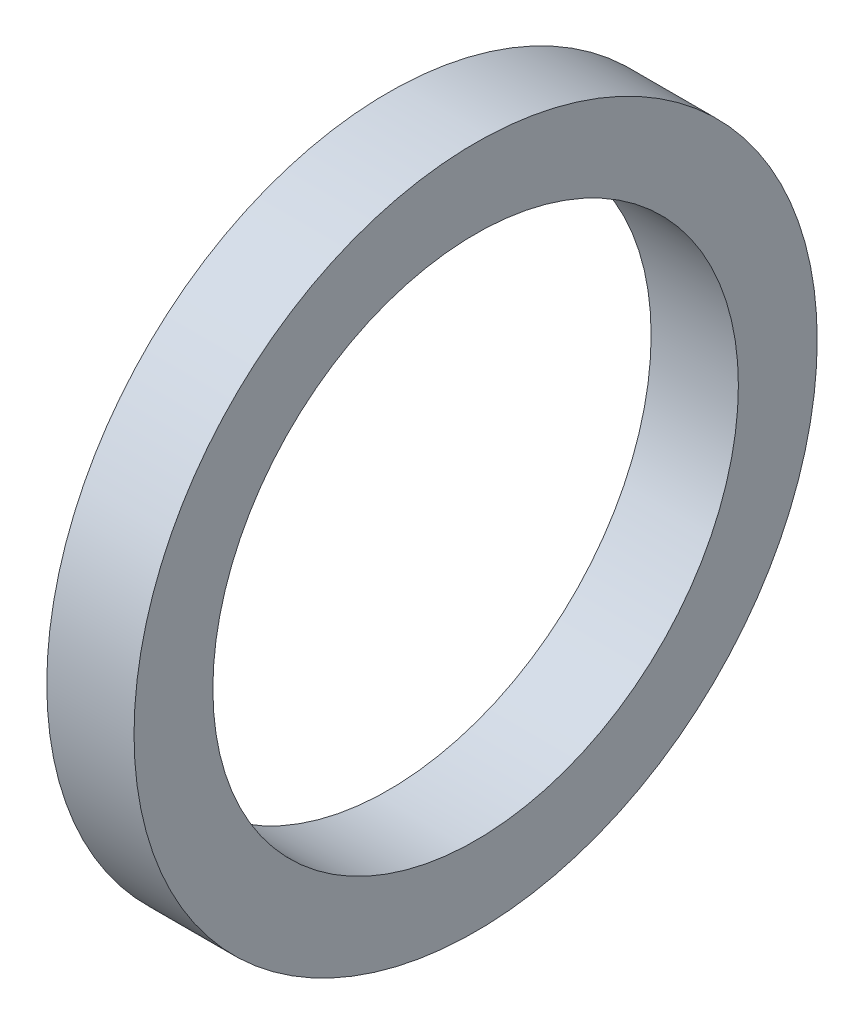
SolidWorks part; units mm, degrees
ref_plane "Front Plane" through (0, 0, 0) normal (0, 0, 1) x (1, 0, 0)
ref_plane "Top Plane" through (0, 0, 0) normal (0, 1, 0) x (1, 0, 0)
ref_plane "Right Plane" through (0, 0, 0) normal (1, 0, 0) x (0, 0, -1)
sketch "Sketch2" plane through (0, 0, 0) normal (0, 0, 1) x (1, 0, 0)
  line L0 (0, 0) -> (58.591, 0) construction
  line L2 (0, 0) -> (18.4, 0)
  line L3 (0, 0) -> (0, 2.5)
  line L4 (0, 2.5) -> (18.4, 2.5)
  line L5 (18.4, 0) -> (18.4, 2.5)
  line L6 (6.0094, 2.5) -> (6.0094, 6)
  line L11 (6.0094, 6) -> (9.9794, 6)
  line L16 (12.9794, 6) -> (12.9794, 3)
  line L17 (12.9794, 3) -> (13.6398, 3)
  line L18 (13.6398, 3) -> (13.6398, 2.5)
  line L19 (13.6398, 2.5) -> (6.0094, 2.5)
  line L22 (13.6398, 2.5) -> (16.1198, 2.5)
  line L23 (13.6398, 2.5) -> (13.6398, 4)
  line L24 (13.6398, 4) -> (16.1198, 4)
  line L25 (16.1198, 2.5) -> (16.1198, 4)
  line L27 (6.0094, 6) -> (9.9794, 6)
  line L28 (6.0094, 6) -> (6.0094, 9)
  line L29 (6.0094, 9) -> (9.9794, 9)
  line L30 (9.9794, 6) -> (9.9794, 9)
  line L31 (6.0094, 9) -> (6.0094, 8.25)
  line L32 (6.0094, 8.25) -> (5.0094, 8.25)
  line L33 (8.6609, 22.001) -> (8.6609, 12.476) construction
  line L34 (5.0094, 12.476) -> (12.3124, 12.476)
  line L35 (9.9794, 9) -> (12.3124, 9)
  line L36 (5.0094, 7.9375) -> (1.8344, 7.9375)
  line L37 (5.0094, 8.25) -> (5.0094, 12.476)
  line L38 (5.0094, 7.9375) -> (5.0094, 13.9365)
  line L39 (5.0094, 13.9365) -> (1.8344, 13.9365)
  line L40 (1.8344, 7.9375) -> (1.8344, 13.9365)
  line L41 (5.0094, 22.001) -> (12.3124, 22.001)
  line L42 (5.0094, 22.001) -> (5.0094, 30.1625)
  line L43 (5.0094, 30.1625) -> (12.3124, 30.1625)
  line L44 (12.3124, 22.001) -> (12.3124, 30.1625)
  line L49 (16.6398, 22.001) -> (16.6398, 7.5)
  line L51 (23.0198, 7.5) -> (23.0198, 6.5)
  line L54 (16.1198, 4) -> (13.6398, 4)
  line L56 (18.0398, 7.5) -> (23.0198, 7.5)
  line L57 (13.3124, 22.001) -> (16.6398, 22.001)
  line L58 (16.1198, 3.5) -> (20.0198, 3.5)
  line L59 (29.9098, 14) -> (26.9098, 11)
  line L60 (4.0094, 31.75) -> (18.0398, 31.75)
  line L61 (18.0398, 7.5) -> (23.0198, 7.5)
  line L62 (18.0398, 7.5) -> (18.0398, 12)
  line L63 (18.0398, 12) -> (23.0198, 12)
  line L64 (23.0198, 7.5) -> (23.0198, 12)
  line L65 (18.0398, 31.75) -> (18.0398, 12)
  line L66 (23.0198, 11) -> (26.9098, 11)
  line L67 (34.8098, 23) -> (31.3098, 19.5)
  line L68 (35.8098, 31) -> (38.7998, 33.99)
  line L69 (29.9098, 14) -> (29.9098, 15)
  line L70 (29.9098, 15) -> (22.9398, 15)
  line L71 (22.9398, 15) -> (21.0398, 15)
  line L72 (18.0398, 7.5) -> (16.6398, 7.5)
  line L73 (21.0398, 15) -> (21.0398, 43)
  line L74 (19.5798, 40) -> (9.6198, 40)
  line L75 (9.6198, 40) -> (4.0094, 40)
  line L76 (21.0398, 43) -> (19.5798, 43)
  line L77 (22.9398, 15) -> (29.9098, 15)
  line L78 (22.9398, 15) -> (22.9398, 21)
  line L79 (22.9398, 21) -> (29.9098, 21)
  line L80 (29.9098, 15) -> (29.9098, 21)
  line L81 (9.6198, 40) -> (19.5798, 40)
  line L82 (9.6198, 40) -> (9.6198, 50)
  line L83 (9.6198, 50) -> (19.5798, 50)
  line L84 (19.5798, 40) -> (19.5798, 50)
  line L85 (4.0094, 40) -> (4.0094, 31.75)
  line L86 (12.9794, 3) -> (12.9794, 2.5)
  line L87 (31.3098, 19.5) -> (29.9098, 19.5)
  line L88 (21.4694, 63.5) -> (21.4694, 51.308)
  line L89 (21.4694, 63.5) -> (25.9398, 63.5)
  line L90 (25.9398, 63.5) -> (25.9398, 25)
  line L91 (27.8398, 25) -> (25.9398, 25)
  line L92 (9.6198, 48) -> (8.1598, 48)
  line L93 (8.1598, 48) -> (8.1598, 53.476)
  line L94 (8.1598, 53.476) -> (19.5798, 53.476)
  line L95 (19.5798, 53.476) -> (19.5798, 50)
  line L96 (13.8698, 63.001) -> (13.8698, 53.476) construction
  line L97 (8.1598, 63.001) -> (19.5798, 63.001)
  line L98 (8.1598, 63.001) -> (8.1598, 68.2625)
  line L99 (8.1598, 68.2625) -> (19.5798, 68.2625)
  line L100 (19.5798, 63.001) -> (19.5798, 68.2625)
  line L101 (12.9794, 6) -> (11.9794, 6)
  line L102 (8.1598, 44.825) -> (4.9848, 44.825)
  line L103 (8.1598, 44.825) -> (8.1598, 54.9365)
  line L104 (8.1598, 54.9365) -> (4.9848, 54.9365)
  line L106 (9.9794, 6) -> (10.8794, 6)
  line L107 (27.8398, 25) -> (34.8098, 25)
  line L108 (34.8098, 25) -> (34.8098, 23)
  line L109 (0, 0) -> (-2, 0)
  line L110 (0, 0) -> (0, 11)
  line L111 (27.8398, 25) -> (34.8098, 25)
  line L112 (27.8398, 25) -> (27.8398, 32.5)
  line L113 (27.8398, 32.5) -> (34.8098, 32.5)
  line L114 (34.8098, 25) -> (34.8098, 32.5)
  line L115 (35.8098, 31) -> (34.8098, 31)
  line L116 (27.8398, 32.5) -> (27.8398, 64.5)
  line L117 (20.5373, 74.025) -> (6.2023, 74.025)
  line L118 (6.2023, 74.025) -> (6.2023, 76.2)
  line L119 (38.7998, 47.29) -> (30.8398, 55.25)
  line L120 (0, 11) -> (-2, 11)
  line L121 (38.7998, 43.815) -> (30.8623, 43.815)
  line L123 (-4.8152, 69.85) -> (1.5348, 76.2)
  line L124 (38.7998, 47.29) -> (38.7998, 33.99)
  line L125 (-2, 0) -> (-2, 11)
  line L126 (38.7998, 37.465) -> (30.8623, 37.465)
  line L127 (30.8623, 43.815) -> (30.8623, 37.465)
  line L128 (6.0094, 2.5) -> (6.0094, 0)
  line L129 (-0.0152, 63.5) -> (-0.0152, 30)
  line L132 (4.9848, 63.5) -> (-0.0152, 63.5)
  line L136 (-1.8152, 30) -> (-11.7752, 30)
  line L138 (-13.7752, 25.4) -> (-2, 25.4)
  line L139 (-2, 25.4) -> (-2, 11.5)
  line L140 (27.8398, 64.5) -> (20.5373, 64.5)
  line L141 (-1.8152, 30) -> (-11.7752, 30)
  line L142 (-1.8152, 30) -> (-1.8152, 39)
  line L143 (-1.8152, 39) -> (-11.7752, 39)
  line L144 (-11.7752, 30) -> (-11.7752, 39)
  line L145 (20.5373, 64.5) -> (20.5373, 74.025)
  line L146 (-12.7752, 37) -> (-12.7752, 47.29)
  line L147 (-12.7752, 37) -> (-11.7752, 37)
  line L148 (30.8398, 55.25) -> (30.8398, 76.2)
  line L149 (11.9794, 6) -> (11.9794, 5.45)
  line L154 (-2, 11.5) -> (0.5, 11.5)
  line L155 (4.9848, 60.6197) -> (24.0348, 60.6197)
  line L160 (4.9848, 60.6197) -> (4.9848, 55.8572)
  line L161 (4.9848, 55.8572) -> (24.0348, 55.8572)
  line L166 (24.0348, 60.6197) -> (24.0348, 55.8572)
  line L167 (4.9848, 60.6197) -> (24.0348, 55.8572) construction
  line L172 (4.9848, 55.8572) -> (24.0348, 60.6197) construction
  line L173 (24.0348, 62.2072) -> (25.9398, 62.2072)
  line L174 (11.9794, 5.45) -> (10.8794, 5.45)
  line L175 (10.8794, 6) -> (10.8794, 5.45)
  line L176 (24.0348, 62.2072) -> (24.0348, 54.2697)
  line L177 (24.0348, 54.2697) -> (25.9398, 54.2697)
  line L178 (25.9398, 62.2072) -> (25.9398, 54.2697)
  line L179 (24.0348, 62.2072) -> (25.9398, 54.2697) construction
  line L180 (24.0348, 54.2697) -> (25.9398, 62.2072) construction
  line L181 (3, 19.6197) -> (15.7, 19.6197)
  line L182 (3, 19.6197) -> (3, 14.8572)
  line L183 (3, 14.8572) -> (15.7, 14.8572)
  line L184 (15.7, 19.6197) -> (15.7, 14.8572)
  line L185 (3, 19.6197) -> (15.7, 14.8572) construction
  line L186 (3, 14.8572) -> (15.7, 19.6197) construction
  line L187 (15.7, 21.2072) -> (16.6398, 21.2072)
  line L188 (15.7, 21.2072) -> (15.7, 13.2697)
  line L189 (15.7, 13.2697) -> (16.6398, 13.2697)
  line L190 (16.6398, 21.2072) -> (16.6398, 13.2697)
  line L191 (15.7, 21.2072) -> (16.6398, 13.2697) construction
  line L192 (15.7, 13.2697) -> (16.6398, 21.2072) construction
  line L193 (0.5, 11.5) -> (0.5, 6.9375)
  line L194 (0.5, 6.9375) -> (1.8344, 6.9375)
  line L195 (23.0198, 6.5) -> (20.0198, 3.5)
  line L196 (4.9848, 63.5) -> (4.9848, 54.9365)
  line L197 (3, 43.825) -> (4.9848, 43.825)
  line L198 (1.8344, 6.9375) -> (1.8344, 7.9375)
  line L199 (6.0094, 0) -> (12.9794, 0)
  line L200 (12.9794, 0) -> (12.9794, 2.5)
  line L201 (18.0398, 31.75) -> (18.0398, 35.875)
  line L202 (18.0398, 35.875) -> (21.0398, 35.875)
  line L203 (30.8398, 76.2) -> (6.2023, 76.2)
  line L204 (2.7573, 69.85) -> (7.2023, 69.85) construction
  line L205 (7.2023, 67.4688) -> (26.2523, 67.4688)
  line L206 (7.2023, 74.025) -> (7.2023, 64.5)
  line L207 (7.2023, 64.5) -> (-1.8152, 64.5)
  line L208 (-1.8152, 64.5) -> (-1.8152, 39)
  line L209 (-12.7752, 47.29) -> (-4.8152, 55.25)
  line L210 (-4.8152, 55.25) -> (-4.8152, 69.85)
  line L211 (7.2023, 67.4688) -> (7.2023, 72.2312)
  line L212 (7.2023, 72.2312) -> (26.2523, 72.2313)
  line L213 (26.2523, 67.4688) -> (26.2523, 72.2313)
  line L214 (26.2523, 73.8187) -> (30.8398, 73.8187)
  line L215 (26.2523, 73.8187) -> (26.2523, 65.8813)
  line L216 (26.2523, 65.8813) -> (30.8398, 65.8813)
  line L217 (30.8398, 73.8187) -> (30.8398, 65.8813)
  line L218 (2.7573, 72.2313) -> (24.9823, 72.2313)
  line L219 (2.7573, 72.2313) -> (2.7573, 67.4687)
  line L220 (2.7573, 67.4687) -> (24.9823, 67.4687)
  line L221 (24.9823, 72.2313) -> (24.9823, 67.4687)
  line L222 (24.9823, 69.85) -> (20.5373, 69.85) construction
  line L223 (21.4694, 51.308) -> (22.9398, 51.308)
  line L224 (22.9398, 51.308) -> (22.9398, 21)
  line L225 (13.6398, 4) -> (13.6398, 12.2697)
  line L226 (13.6398, 12.2697) -> (13.3124, 12.2697)
  line L227 (13.3124, 12.2697) -> (13.3124, 22.001)
  line L228 (12.3124, 9) -> (12.3124, 12.476)
  line L229 (-1.8152, 30) -> (-0.0152, 30)
  line L230 (8.1598, 65.6317) -> (2.7573, 65.6317) construction
  line L231 (19.5798, 65.6317) -> (24.9823, 65.6317) construction
  line L232 (1.5348, 76.2) -> (6.2023, 76.2)
  line L233 (-11.7752, 30) -> (-13.7752, 30)
  line L234 (-13.7752, 30) -> (-13.7752, 25.4)
  line L235 (3, 13.9365) -> (3, 43.825)
  line L236 (4.9848, 54.9365) -> (4.9848, 44.825)
  line L237 (4.9848, 43.825) -> (4.9848, 44.825)
  circle A0 centre (26.8898, 25.95) radius 0.95
  circle A1 centre (21.9898, 15.95) radius 0.95
  circle A2 centre (17.3398, 8.2) radius 0.7
  circle A3 centre (10.4294, 6.45) radius 0.45
  circle A4 centre (-0.9152, 30.9) radius 0.9
  point P7 (24.9873, 58.2385)
  point P131 (16.1699, 17.2385)
  point P135 (14.5098, 58.2385)
  point P146 (9.35, 17.2385)
sketch "Sketch3" plane through (0, 0, 0) normal (0, 0, 1) x (1, 0, 0)
  line L0 (-1.8152, 30) -> (-1.8152, 39) construction
  line L1 (-1.8152, 30) -> (-11.7752, 30) construction
  line L2 (-11.7752, 30) -> (-11.7752, 39) construction
  line L3 (-1.8152, 39) -> (-11.7752, 39) construction
  line L4 (-1.8152, 30) -> (-1.8152, 39)
  line L5 (-1.8152, 30) -> (-11.7752, 30)
  line L6 (-11.7752, 30) -> (-11.7752, 39)
  line L7 (-1.8152, 39) -> (-11.7752, 39)
revolve "Revolve1" add sketch "Sketch3" angle 360 about L0
